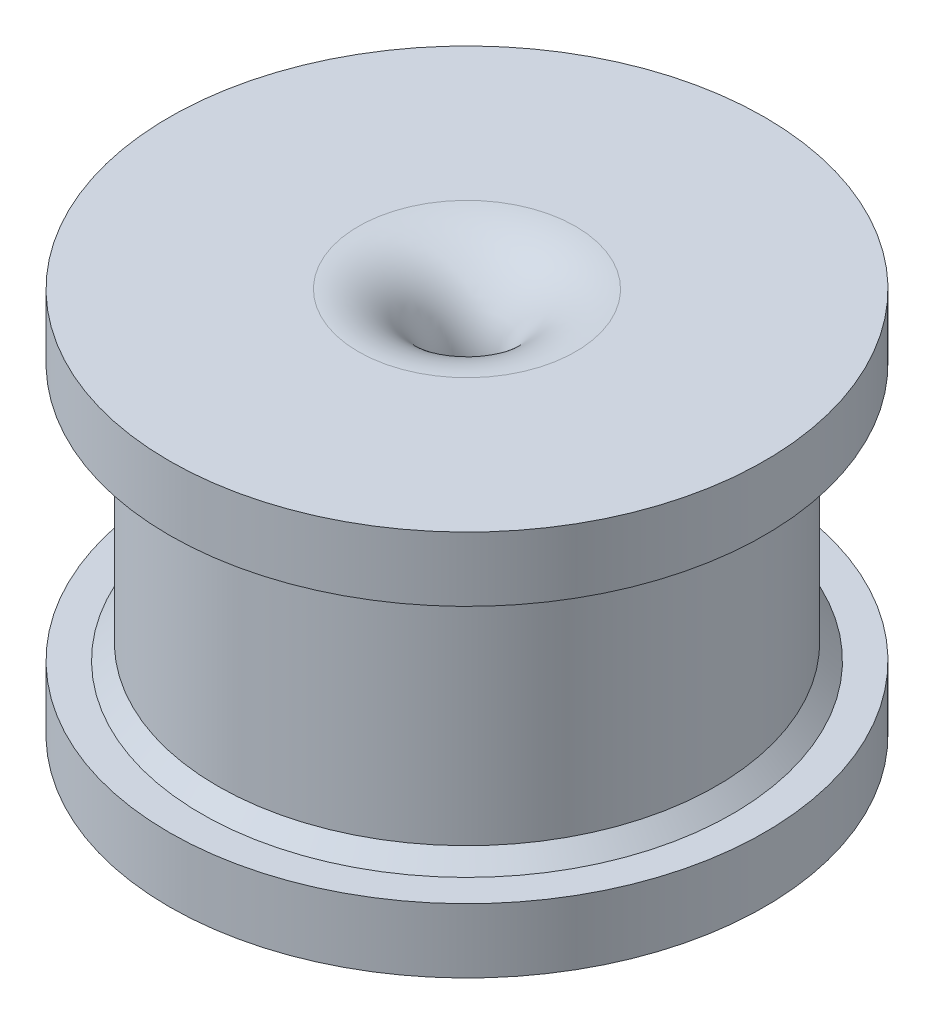
SolidWorks part; units mm, degrees
ref_plane "Front Plane" through (0, 0, 0) normal (0, 0, 1) x (1, 0, 0)
ref_plane "Top Plane" through (0, 0, 0) normal (0, 1, 0) x (1, 0, 0)
ref_plane "Right Plane" through (0, 0, 0) normal (1, 0, 0) x (0, 0, -1)
sketch "Sketch1" plane through (0, 0, 0) normal (0, 1, 0) x (1, 0, 0)
  circle A0 centre (0, 0) radius 15.5
  circle A1 centre (0, 0) radius 1.75
  dimension "D1" = 31
  dimension "D2" = 3.5
extrude "Boss-Extrude1" add sketch "Sketch1" along normal blind 16
sketch "Sketch2" plane through (0, 16, 0) normal (0, 1, 0) x (1, 0, 0)
  circle A0 centre (0, 0) radius 18.5
  circle A1 centre (0, 0) radius 1.75
  circle A2 centre (0, 0) radius 1.75 construction
  circle A3 centre (0, 0) radius 15.5 construction
  dimension "D1" = 3
extrude "Boss-Extrude2" add sketch "Sketch2" along normal blind 4
sketch "Sketch3" plane through (0, 0, 0) normal (0, -1, 0) x (1, 0, 0)
  circle A0 centre (0, 0) radius 18.5
  circle A1 centre (0, 0) radius 1.75
  circle A2 centre (0, 0) radius 18.5 construction
  circle A3 centre (0, 0) radius 1.75 construction
extrude "Boss-Extrude3" add sketch "Sketch3" along normal blind 4
fillet "Fillet1" radius 5 2 edges at (0, -4, -1.75) (0, 20, 1.75)
chamfer "Chamfer1" distance 1 angle 45 2 edges at (0, 16, 15.5) (0, 0, 15.5)
